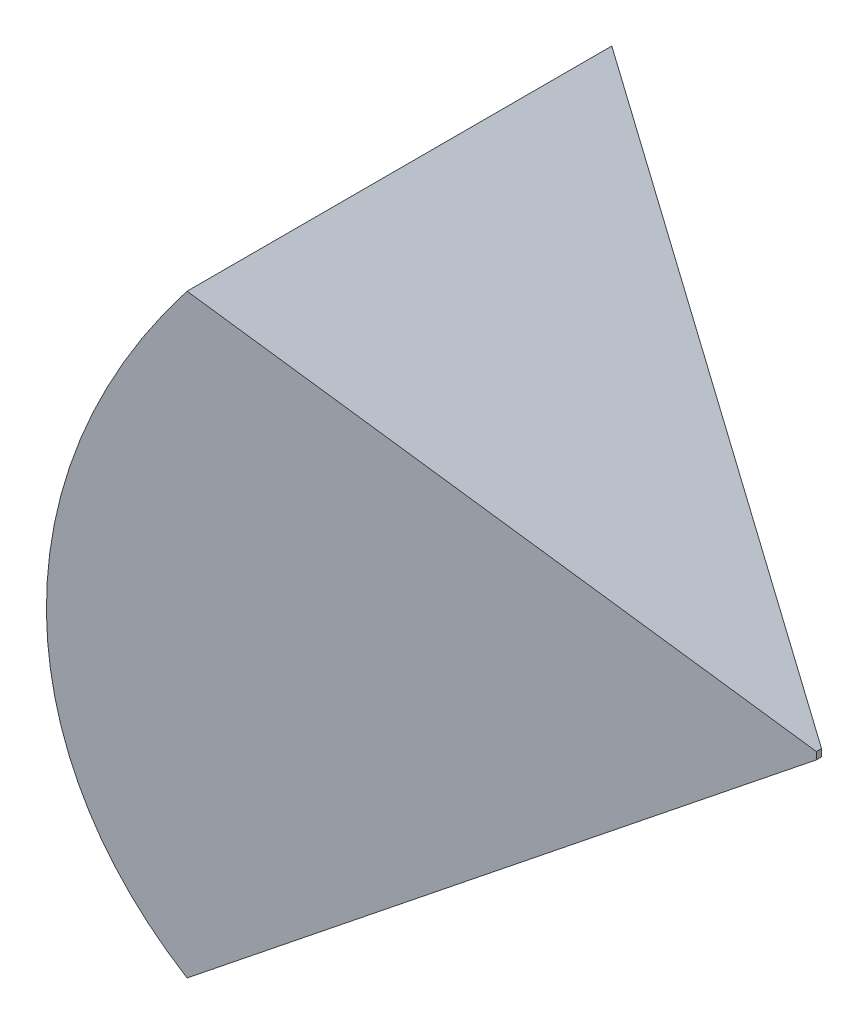
SolidWorks part; units mm, degrees
ref_plane "Front Plane" through (0, 0, 0) normal (0, 0, 1) x (1, 0, 0)
ref_plane "Top Plane" through (0, 0, 0) normal (0, 1, 0) x (1, 0, 0)
ref_plane "Right Plane" through (0, 0, 0) normal (1, 0, 0) x (0, 0, -1)
sketch "Sketch3" plane through (0, 0, 0) normal (0, 0, 1) x (1, 0, 0)
  line L0 (0, 0) -> (-16383.0409, 11471.5287)
  line L2 (0, 0) -> (-16383.0409, -11471.5287)
  arc A0 (-16383.0409, 11471.5287) -> (-16383.0409, -11471.5287) centre (0, 0) ccw
  dimension "D1" = 20000
  dimension "D2" = 70
extrude "Boss-Extrude1" add sketch "Sketch3" along normal blind 20000
sketch "Sketch20" plane through (0, 0, 0) normal (0, 1, 0) x (1, 0, 0)
  line L12 (0, -10000) -> (-20000, -20000)
  line L13 (0, -20000) -> (0, 0) construction
  line L14 (-20000, -20000) -> (0, -20000)
  line L15 (0, -20000) -> (0, -10000)
extrude "Cut-Extrude1" cut sketch "Sketch20" against normal through all both and the other way through all
sketch "Sketch22" plane through (0, 0, 0) normal (0, 1, 0) x (1, 0, 0)
  line L0 (0, -10000) -> (-20000, 0)
  line L1 (-20000, 0) -> (0, 0)
  line L2 (0, 0) -> (0, -10000)
extrude "Cut-Extrude2" cut sketch "Sketch22" against normal through all both and the other way through all
sketch "Sketch23" plane through (0, 0, 0) normal (0, 1, 0) x (1, 0, 0)
  line L0 (-200, -10100) -> (-200, -9900)
  line L1 (-16383.0409, -18191.5204) -> (0, -10000) construction
  line L2 (0, -10000) -> (-16383.0409, -1808.4796) construction
  line L3 (-200, -9900) -> (0, -10000)
  line L4 (0, -10000) -> (-200, -10100)
  dimension "D1" = 200
extrude "Cut-Extrude3" cut sketch "Sketch23" against normal through all both and the other way through all
